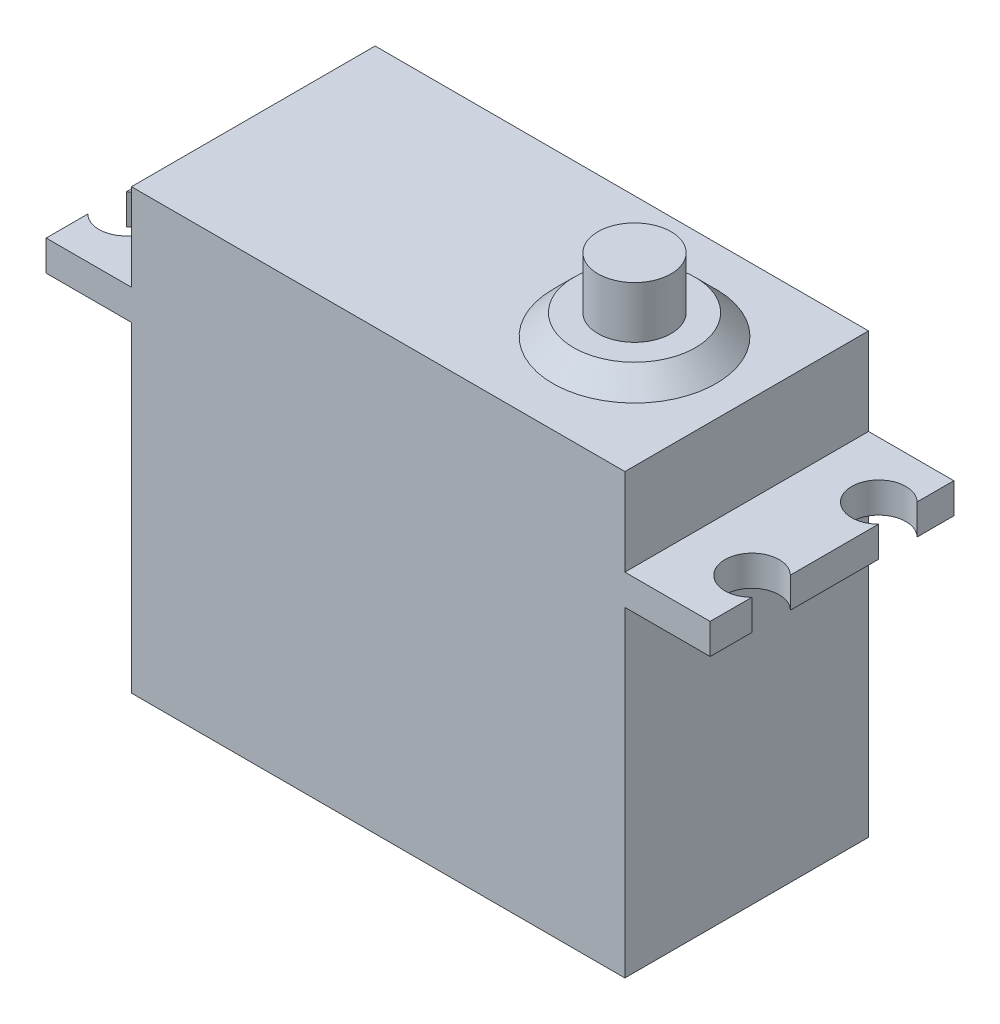
SolidWorks part; units mm, degrees
material "ABS"
ref_plane "前基準面" through (0, 0, 0) normal (0, 0, 1) x (1, 0, 0)
ref_plane "上基準面" through (0, 0, 0) normal (0, 1, 0) x (1, 0, 0)
ref_plane "右基準面" through (0, 0, 0) normal (1, 0, 0) x (0, 0, -1)
sketch "草圖1" plane through (0, 0, 0) normal (0, 0, 1) x (1, 0, 0)
  line L0 (-4.1528, 15.9019) -> (-4.1528, -10.4481)
  line L1 (-4.1528, -10.4481) -> (36.3472, -10.4481)
  line L2 (36.3472, -10.4481) -> (36.3472, 15.9019)
  line L3 (-4.1528, 15.9019) -> (-11.1528, 15.9019)
  line L4 (-11.1528, 15.9019) -> (-11.1528, 18.4019)
  line L5 (-11.1528, 18.4019) -> (-4.1528, 18.4019)
  line L6 (-4.1528, 18.4019) -> (-4.1528, 25.5519)
  line L7 (-4.1528, 25.5519) -> (36.3472, 25.5519)
  line L8 (36.3472, 25.5519) -> (36.3472, 18.4019)
  line L9 (36.3472, 18.4019) -> (43.3472, 18.4019)
  line L10 (43.3472, 18.4019) -> (43.3472, 15.9019)
  line L11 (43.3472, 15.9019) -> (36.3472, 15.9019)
  dimension "D1" = 40.5
  dimension "D2" = 26.35
  dimension "D3" = 26.35
  dimension "D4" = 2.5
  dimension "D5" = 2.5
  dimension "D6" = 7
  dimension "D7" = 7
  dimension "D8" = 40.5
  dimension "D9" = 36
extrude "填料-伸長1" add sketch "草圖1" along normal blind 20 contours L6 L7 L8 L9 L10 L11 L2 L1 L0 L3 L4 L5
sketch "草圖2" plane through (0, 18.4019, 0) normal (0, 1, 0) x (1, 0, 0)
  line L0 (43.3472, -20) -> (43.3472, 0) construction
  line L2 (36.3472, 0) -> (43.3472, 0) construction
  circle A0 centre (41.786, -4.6) radius 2.225
  circle A1 centre (41.786, -15) radius 2.225
  dimension "D1" = 4.45
  dimension "D2" = 4.45
  dimension "D3" = 10.4
  dimension "D4" = 4.6
  dimension "D5" = 1.5612
extrude "除料-伸長4" cut sketch "草圖2" against normal blind 5 contours A1 | A0
sketch "草圖3" plane through (0, 18.4019, 0) normal (0, 1, 0) x (1, 0, 0)
  line L0 (-11.1528, 0) -> (-4.1528, 0) construction
  line L1 (-11.1528, -20) -> (-11.1528, 0) construction
  circle A0 centre (-9.5928, -4.6) radius 2.225
  circle A1 centre (-9.5928, -15) radius 2.225
  dimension "D1" = 4.45
  dimension "D2" = 4.45
  dimension "D3" = 10.4
  dimension "D4" = 4.6
  dimension "D5" = 1.56
extrude "除料-伸長5" cut sketch "草圖3" against normal blind 5 contours A1 | A0
sketch "草圖4" plane through (0, 25.5519, 0) normal (0, 1, 0) x (1, 0, 0)
  line L0 (-4.1528, 0) -> (36.3472, 0) construction
  circle A0 centre (27.1397, -10) radius 5
  dimension "D1" = 10
  dimension "D2" = 10
extrude "填料-伸長3" add sketch "草圖4" along normal blind 1.7 contours A0
chamfer "導角3" distance 1.7 angle 45 1 edges at (22.1397, 25.5519, 10)
sketch "草圖5" plane through (0, 27.2519, 0) normal (0, 1, 0) x (1, 0, 0)
  circle A0 centre (27.1397, -10) radius 3
  circle A1 centre (27.1397, -10) radius 5 construction
  dimension "D2" = 6
  dimension "D1" = 0
extrude "填料-伸長4" add sketch "草圖5" along normal blind 4.25
